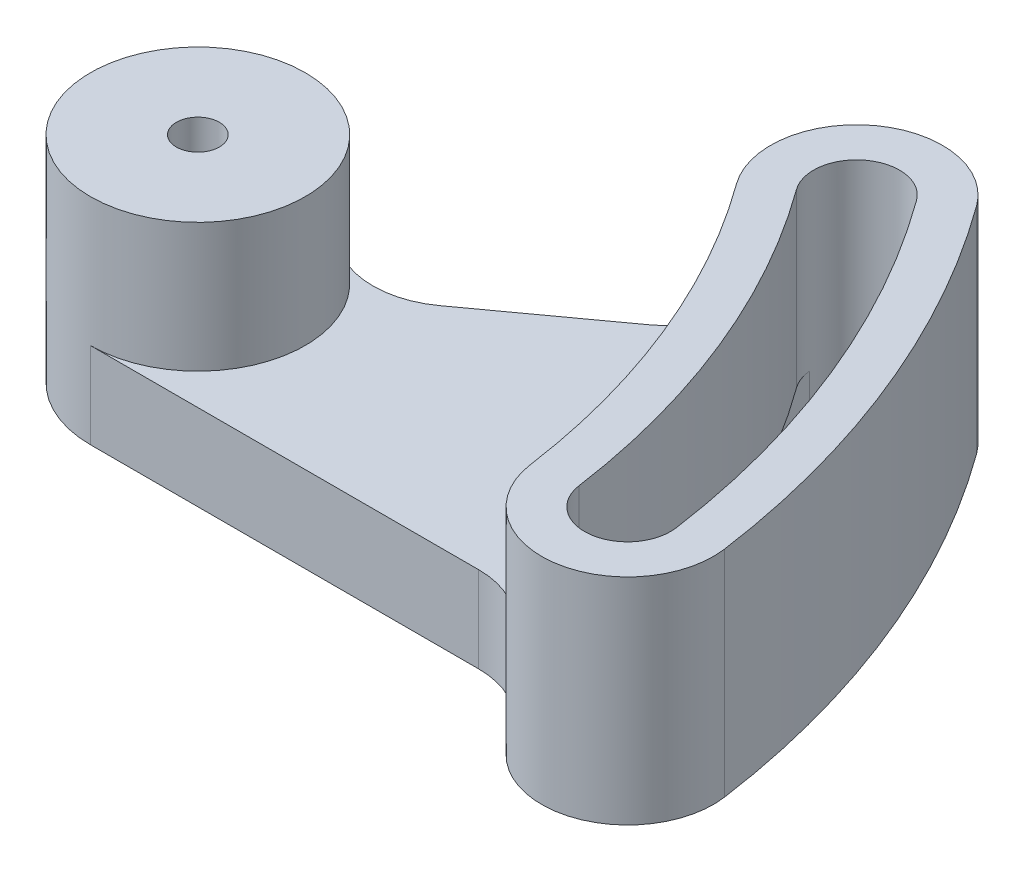
SolidWorks part; units mm, degrees
ref_plane "Front Plane" through (0, 0, 0) normal (0, 0, 1) x (1, 0, 0)
ref_plane "Top Plane" through (0, 0, 0) normal (0, 1, 0) x (1, 0, 0)
ref_plane "Right Plane" through (0, 0, 0) normal (1, 0, 0) x (0, 0, -1)
sketch "Sketch1" plane through (0, 0, 0) normal (0, 1, 0) x (1, 0, 0)
  circle A0 centre (0, 0) radius 25
  circle A1 centre (0, 0) radius 5
  dimension "D1" = 50
  dimension "D2" = 10
extrude "Boss-Extrude1" add sketch "Sketch1" along normal blind 50 contours A0 | A1
sketch "Sketch3" plane through (0, 0, 0) normal (0, 1, 0) x (1, 0, 0)
  line L0 (0, 0) -> (125, 0) construction
  line L1 (0, 0) -> (88.7807, 64.503) construction
  line L2 (125, -25) -> (0, -25)
  line L3 (20.2254, 14.6946) -> (88.7807, 64.503)
  line L4 (125, -25) -> (125, -58.224) construction
  arc A0 (88.7807, 64.503) -> (125, -25) centre (-73.0226, -53.0541) cw
  circle A1 centre (0, 0) radius 25 construction
  circle A3 centre (0, 0) radius 25
  circle A4 centre (0, 0) radius 25
  point P7 (88.7807, 64.503)
  point P14 (17.4856, -17.8677)
  point P15 (0, -25)
  dimension "D2" = 200
  dimension "D1" = 125
  dimension "D3" = 0
  dimension "D4" = 36
extrude "Boss-Extrude4" add sketch "Sketch3" along normal blind 20 contours A4 L2 A0 L3 region at (72.652, 0, -8.4007)
sketch "Sketch4" plane through (0, 20, 0) normal (0, 1, 0) x (1, 0, 0)
  line L2 (0, -25) -> (125, -25)
  line L3 (88.7807, 64.503) -> (20.2254, 14.6946)
  line L4 (0, -25) -> (125, -25)
  line L5 (88.7807, 64.503) -> (20.2254, 14.6946)
  arc A0 (88.7807, 64.503) -> (125, -25) centre (-73.0226, -53.0541) cw construction
  arc A1 (134.9011, -23.5973) -> (96.8709, 70.3808) centre (-73.0226, -53.0541) ccw
  arc A2 (0, -25) -> (20.2254, 14.6946) centre (0, 0) ccw
  arc A3 (125, -25) -> (88.7807, 64.503) centre (-73.0226, -53.0541) ccw
  arc A4 (0, -25) -> (20.2254, 14.6946) centre (0, 0) ccw
  arc A5 (125, -25) -> (88.7807, 64.503) centre (-73.0226, -53.0541) ccw
  arc A6 (115.0989, -26.4027) -> (80.6906, 58.6251) centre (-73.0226, -53.0541) ccw
  arc A7 (115.0989, -26.4027) -> (134.9011, -23.5973) centre (125, -25) ccw
  arc A8 (96.8709, 70.3808) -> (80.6906, 58.6251) centre (88.7807, 64.503) ccw
  arc A9 (144.8023, -22.1946) -> (104.9611, 76.2587) centre (-73.0226, -53.0541) ccw
  arc A10 (104.9611, 76.2587) -> (72.6004, 52.7473) centre (88.7807, 64.503) ccw
  arc A11 (105.1977, -27.8054) -> (72.6004, 52.7473) centre (-73.0226, -53.0541) ccw
  arc A12 (105.1977, -27.8054) -> (144.8023, -22.1946) centre (125, -25) ccw
  point P5 (112.3726, 21.97)
  arc M15 (125, -25) -> (88.7807, 64.503) centre (-73.0226, -53.0541) ccw
  line M16 (88.7807, 64.503) -> (20.2254, 14.6946)
  dimension "D2" = 10
  dimension "D3" = 10
  dimension "D1" = 0
extrude "Boss-Extrude5" add sketch "Sketch4" along normal blind 30 and the other way blind 20 contours A11 A12 A9 A10 L5 A8 A1 A7 A6 L4 | A11 L4 A6 L5 | A6 A8 A1 A7 region at (96.5108, 20, -16.6831) region at (109.8363, 20, 26.5027)
fillet "Fillet2" radius 20 3 edges at (20.2254, 10, -14.6946) (104.7777, 10, 25) (72.6004, 10, -52.7473)
shell "Shell2" thickness 10 removed face at (66.8425, 0, -14.2289)
sketch "Sketch7" plane through (0, 40, 0) normal (0, -1, 0) x (-1, 0, 0)
  arc A4 (-80.6906, 58.6251) -> (-96.8709, 70.3808) centre (-88.7807, 64.503) ccw
  arc A5 (-96.8709, 70.3808) -> (-134.9011, -23.5973) centre (73.0226, -53.0541) ccw
  arc A6 (-134.9011, -23.5973) -> (-115.0989, -26.4027) centre (-125, -25) ccw
  arc A7 (-80.6906, 58.6251) -> (-115.0989, -26.4027) centre (73.0226, -53.0541) ccw
  arc A8 (-80.6906, 58.6251) -> (-96.8709, 70.3808) centre (-88.7807, 64.503) ccw
  arc A9 (-96.8709, 70.3808) -> (-134.9011, -23.5973) centre (73.0226, -53.0541) ccw
  arc A10 (-134.9011, -23.5973) -> (-115.0989, -26.4027) centre (-125, -25) ccw
  arc A11 (-80.6906, 58.6251) -> (-115.0989, -26.4027) centre (73.0226, -53.0541) ccw
  dimension "D1" = 0
extrude "Cut-Extrude2" cut sketch "Sketch4<3>" against normal through all both and the other way through all contours A1 A8 L4 A6 A7 M16 M15 | A6 L4 M15 M16 region at (105.899, 20, -19.7246) region at (112.9902, 20, -21.9525)
sketch "Sketch4<3>" plane through (0, 20, 0) normal (0, 1, 0) x (1, 0, 0) same geometry as "Sketch4"
